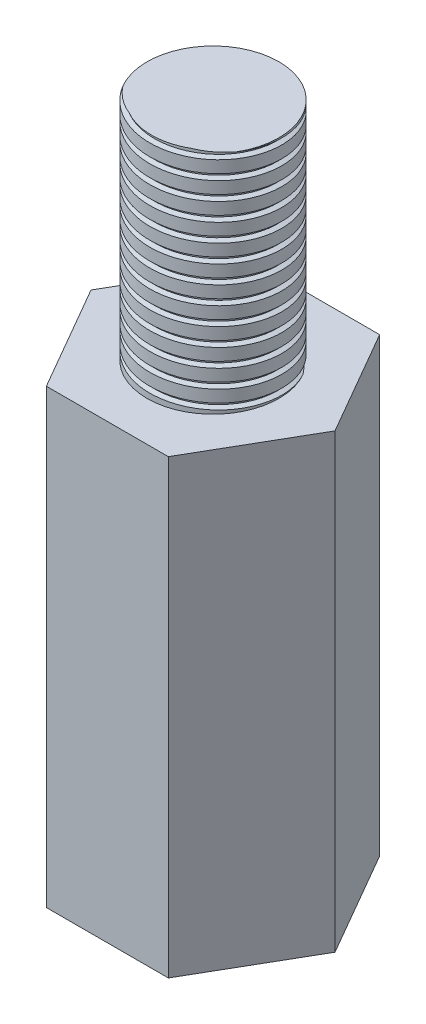
SolidWorks part; units mm, degrees
note: The reader was unsure of these and kept them because the rebuilt part matched: shared geometry of "草图1<3>".
ref_plane "前视基准面" through (0, 0, 0) normal (0, 0, 1) x (1, 0, 0)
ref_plane "上视基准面" through (0, 0, 0) normal (0, 1, 0) x (1, 0, 0)
ref_plane "右视基准面" through (0, 0, 0) normal (1, 0, 0) x (0, 0, -1)
sketch "草图1" plane through (0, 0, 0) normal (0, 1, 0) x (1, 0, 0)
  line L0 (0, 0) -> (0, 4.5761) construction
  line L1 (1.351, -2.34) -> (2.702, 0)
  line L2 (2.702, 0) -> (1.351, 2.34)
  line L3 (1.351, 2.34) -> (-1.351, 2.34)
  line L4 (-1.351, 2.34) -> (-2.702, 0)
  line L5 (-2.702, 0) -> (-1.351, -2.34)
  line L6 (-1.351, -2.34) -> (1.351, -2.34)
  line L7 (0, 4.5761) -> (0, -3.6794) construction
  circle A0 centre (0, 0) radius 2.34 construction
  circle A1 centre (0, 0) radius 1.46
  dimension "D1" = 4.68
  dimension "D2" = 2.92
extrude "凸台-拉伸1" add sketch "草图1" along normal blind 10 contours A1 | L5 L6 L1 L2 L3 L4 A1
extrude "切除-拉伸1" cut sketch "草图1<3>" along normal blind 5 contours A1
sketch "草图1<3>" plane through (0, 0, 0) normal (0, 1, 0) x (1, 0, 0) same geometry as "草图1"
sketch "草图2" plane through (0, 10, 0) normal (0, 1, 0) x (1, 0, 0)
  circle A0 centre (0, 0) radius 1.46
  dimension "D1" = 2.92
extrude "凸台-拉伸2" add sketch "草图2" along normal blind 5 separate body
ref_plane "基准面1" through (0, 0, 0) normal (0, 0, -1) x (-1, 0, 0)
sketch "草图4" plane through (0, 0, 0) normal (0, 0, -1) x (-1, 0, 0)
  line L0 (0, 0) -> (0, 28.5702) construction
  line L1 (-1.56, 10) -> (-1.56, 10.2)
  line L2 (-1.56, 10.2) -> (-1.36, 10.1333)
  line L3 (-1.36, 10.0667) -> (-1.56, 10)
  line L4 (-1.26, 10.1) -> (-2.0659, 10.1) construction
  line L5 (-2.0659, 10.1) -> (-0.8933, 10.1) construction
  line L7 (-1.46, 15) -> (-1.46, 10) construction
  line L8 (-1.36, 10.1333) -> (-1.36, 10.0667)
  line L9 (-1.46, 10) -> (1.46, 10) construction
  point P14 (0, 0)
  point P15 (0, 0)
  dimension "D1" = 0.1
  dimension "D2" = 0.1
  dimension "D3" = 0.1
  dimension "D4" = 0.3
  dimension "D5" = 0.2
  dimension "D6" = 0.1
  dimension "D7" = 0.0667
  dimension "D8" = 0.0667
ref_plane "基准面2" through (0, 10.1, 0) normal (0, 1, 0) x (1, 0, 0)
sketch "草图5" plane through (0, 10.1, 0) normal (0, 1, 0) x (1, 0, 0)
  circle A0 centre (0, 0) radius 1.46
  dimension "D1" = 2.92
curve "螺旋线/涡状线1" pitch 0.4 height 7.5 turns 18.75
sweep "切除-扫描1" cut profiles "草图4" path "螺旋线/涡状线1"
sketch "草图6" plane through (0, 0, 0) normal (0, -1, 0) x (1, 0, 0)
  circle A0 centre (0, 0) radius 1.46
curve "螺旋线/涡状线2" pitch 0.4 height 9.5 turns 23.75
sketch "草图7" plane through (0, 0, 0) normal (0, 0, -1) x (-1, 0, 0)
  line L0 (1.46, 0.2) -> (1.66, 0.1333)
  line L1 (1.66, 0.0667) -> (1.46, 0)
  line L2 (1.46, 0.2) -> (1.46, 0)
  line L3 (1.66, 0.1333) -> (1.66, 0.0667)
  line L8 (1.351, 0) -> (-1.351, 0) construction
  dimension "D1" = 0.2
  dimension "D3" = 1.46
  dimension "D4" = 0.2
sweep "切除-扫描2" cut profiles "草图7" path "螺旋线/涡状线2"
equation "\"chang\"= 20mm"
equation "\"r\"= 2.92mm"
equation "\"luowengao\"= 6.5mm"
equation "\"rr\"= 4.68mm"
equation "\"D1@草图1\"=\"rr\""
equation "\"D2@草图1\"=\"r\""
equation "\"D1@凸台-拉伸1\"=\"chang\""
equation "\"D1@切除-拉伸1\"=\"luowengao\"+5mm"
equation "\"D1@草图2\"=\"r\""
equation "\"D1@凸台-拉伸2\"=\"luowengao\""
